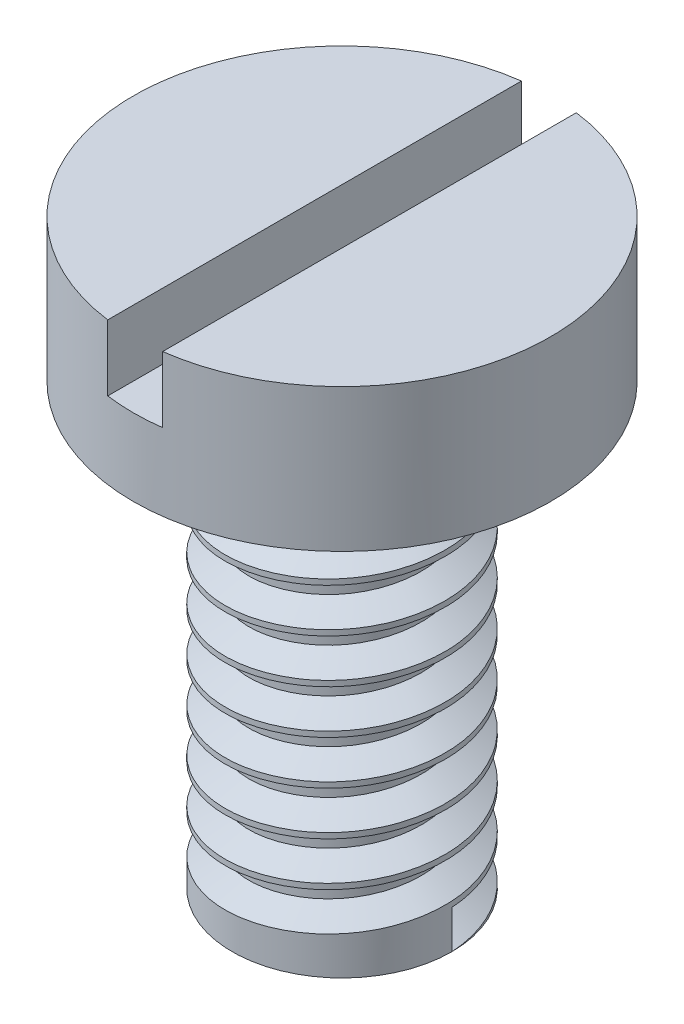
SolidWorks part; units mm, degrees
material "Brass"
ref_plane "Front Plane" through (0, 0, 0) normal (0, 0, 1) x (1, 0, 0)
ref_plane "Top Plane" through (0, 0, 0) normal (0, 1, 0) x (1, 0, 0)
ref_plane "Right Plane" through (0, 0, 0) normal (1, 0, 0) x (0, 0, -1)
sketch "Sketch1" plane through (0, 0, 0) normal (0, 1, 0) x (1, 0, 0)
  circle A0 centre (0, 0) radius 1.9
  dimension "D1" = 3.8
extrude "Boss-Extrude1" add sketch "Sketch1" along normal blind 1.3
sketch "Sketch2" plane through (0, 0, 0) normal (0, -1, 0) x (1, 0, 0)
  circle A0 centre (0, 0) radius 1
  dimension "D1" = 2
extrude "Boss-Extrude2" add sketch "Sketch2" along normal blind 4
thread "Thread1" pitch 0.4 method cut profile "Thread Profile1" start angle 0, offset 0, length 0, pitch 0.4, diameter 2
ref_plane "Plane1" through (1, -4, 0) normal (0, 0, 1) x (1, 0, 0)
sketch "Thread Profile1" plane through (1, -4, 0) normal (0, 0, 1) x (1, 0, 0)
  line L0 (0, 0) -> (0, 0.4) construction
  line L11 (0, 0) -> (0, 0.35)
  line L12 (0, 0.35) -> (-0.2165, 0.225)
  line L13 (-0.2165, 0.225) -> (-0.2165, 0.125)
  line L15 (-0.2165, 0.125) -> (0, 0)
  line L17 (-0.2165, 0.175) -> (0, 0.175) construction
  point P2 (0, 0)
  dimension "Pitch" = 0.4
  dimension "Profile_Angle" = 60
  dimension "Profile_Land" = 0.1
  dimension "Profile_Height" = 0.2165
sketch "Sketch6" plane through (0, 1.3, 0) normal (0, 1, 0) x (1, 0, 0)
  line L0 (0, -1000) -> (0, 49000) construction
  line L2 (0.25, -2) -> (-0.25, -2)
  line L3 (0.25, -2) -> (0.25, 2)
  line L4 (0.25, 2) -> (-0.25, 2)
  line L5 (-0.25, -2) -> (-0.25, 2)
  line L6 (0.25, -2) -> (-0.25, 2) construction
  line L7 (0.25, 2) -> (-0.25, -2) construction
  point P1 (0, 0)
  dimension "D1" = 0.5
  dimension "D2" = 4
extrude "Cut-Extrude1" cut sketch "Sketch6" against normal blind 0.6
